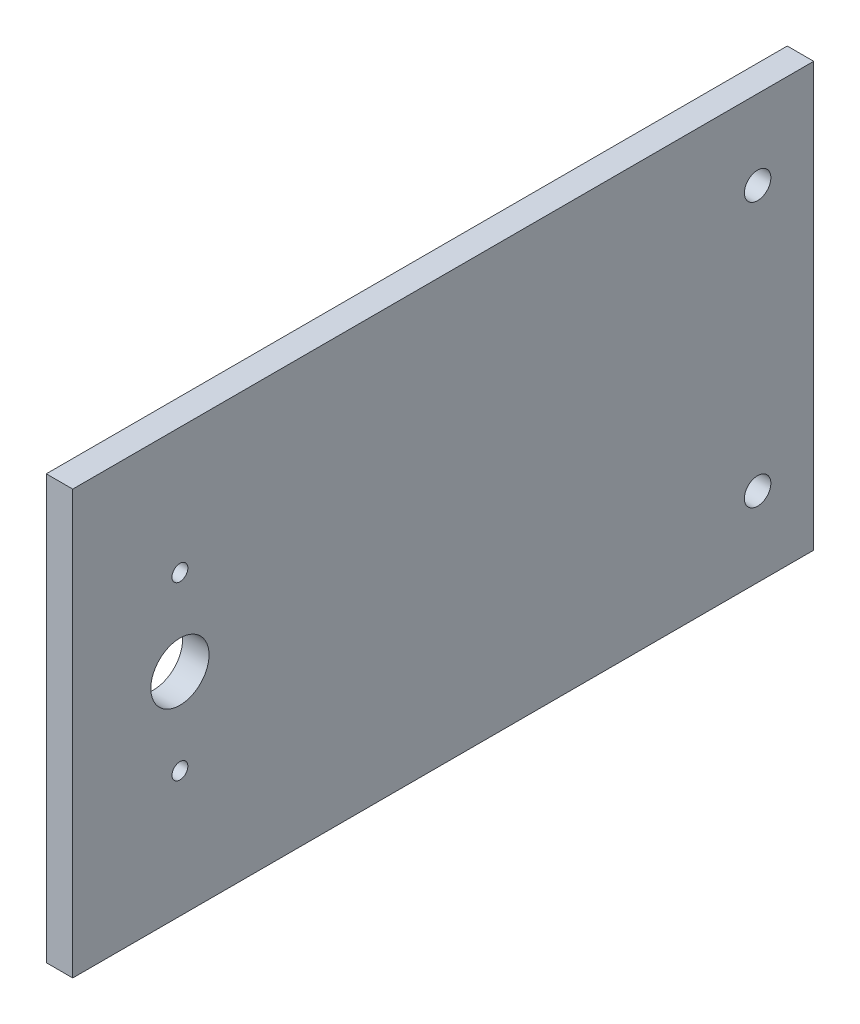
SolidWorks part; units mm, degrees
ref_plane "Front Plane" through (0, 0, 0) normal (1, 0, 0) x (0, 1, 0)
ref_plane "Top Plane" through (0, 0, 0) normal (0, 0, 1) x (0, 1, 0)
ref_plane "Right Plane" through (0, 0, 0) normal (0, 1, 0) x (-1, 0, 0)
sketch "Sketch1" plane through (0, 0, 0) normal (1, 0, 0) x (0, 1, 0)
  line L0 (0, 70) -> (0, -70) construction
  line L1 (-40, -70) -> (40, -70)
  line L2 (-40, -70) -> (-40, 70)
  line L3 (-40, 70) -> (40, 70)
  line L4 (40, -70) -> (40, 70)
  line L5 (-40, -70) -> (40, 70) construction
  line L6 (-40, 70) -> (40, -70) construction
  line L7 (-40, 49.75) -> (40, 49.75) construction
  line L9 (-25, -59.4) -> (25, -59.4) construction
  line L10 (-25, -59.4) -> (-25, 59.4) construction
  line L11 (-25, 59.4) -> (25, 59.4) construction
  line L12 (25, -59.4) -> (25, 59.4) construction
  line L13 (-25, -59.4) -> (25, 59.4) construction
  line L14 (-25, 59.4) -> (25, -59.4) construction
  circle A5 centre (0, 49.75) radius 5.5
  circle A6 centre (-16.22, 49.75) radius 1.5
  circle A7 centre (16.22, 49.75) radius 1.5
  circle A8 centre (-25, -59.4) radius 2.5
  circle A9 centre (25, -59.4) radius 2.5
  point P0 (0, 0)
  point P14 (0, 0)
  dimension "D5" = 16.22
  dimension "D6" = 10.6
  dimension "D7" = 50
  dimension "D8" = 11
  dimension "D4" = 3
  dimension "D9" = 5
  dimension "D10" = 5
  dimension "D1" = 80
  dimension "D2" = 140
  dimension "D3" = 119.75
extrude "Boss-Extrude1" add sketch "Sketch1" along normal blind 5
